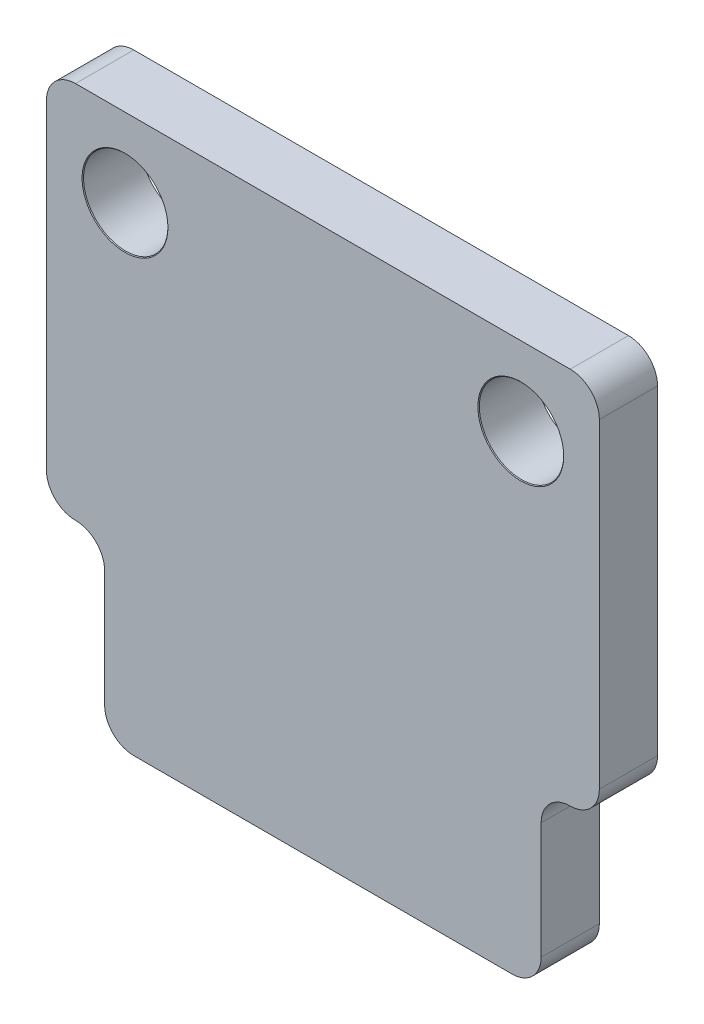
SolidWorks part; units mm, degrees
ref_plane "Plan de face" through (0, 0, 0) normal (0, 0, 1) x (1, 0, 0)
ref_plane "Plan de dessus" through (0, 0, 0) normal (0, 1, 0) x (1, 0, 0)
ref_plane "Plan de droite" through (0, 0, 0) normal (1, 0, 0) x (0, 0, -1)
sketch "Esquisse1" plane through (0, 0, 0) normal (0, 0, 1) x (1, 0, 0)
  line L0 (0, 0) -> (0, 19) construction
  line L1 (-9.5, 19) -> (9.5, 19)
  line L2 (9.5, 19) -> (9.5, 6)
  line L3 (9.5, 6) -> (7.5, 6)
  line L4 (7.5, 6) -> (7.5, 0)
  line L5 (7.5, 0) -> (-7.5, 0)
  line L6 (-7.5, 6) -> (-7.5, 0)
  line L7 (-9.5, 6) -> (-7.5, 6)
  line L8 (-9.5, 19) -> (-9.5, 6)
  dimension "D2" = 19
  dimension "D4" = 6
  dimension "D1" = 19
  dimension "D3" = 15
extrude "Boss.-Extru.1" add sketch "Esquisse1" along normal blind 2
fillet "Congé3" radius 1 8 edges at (9.5, 19, 1) (9.5, 6, 1) (7.5, 6, 1) (7.5, 0, 1) (-7.5, 0, 1) (-7.5, 6, 1) (-9.5, 6, 1) (-9.5, 19, 1)
hole_wizard "Dégagement M2.51" positions "Esquisse3D1" profile "Esquisse2" hole size "M2.5" standard "Ansi Metric" end condition through all
sketch3d "Esquisse3D1"
  line L0 (-9.5, 18, 2) -> (-9.5, 7, 2) construction
  line L1 (8.5, 19, 2) -> (-8.5, 19, 2) construction
  line L2 (9.5, 7, 2) -> (9.5, 18, 2) construction
  point P0 (-6.8, 16.3, 2)
  point P2 (6.8, 16.3, 2)
  dimension "D1" = 2.7
  dimension "D2" = 2.7
  dimension "D3" = 2.7
  dimension "D4" = 2.7
sketch "Esquisse2" plane through (-6.8, 16.3, 2) normal (1, 0, 0) x (0, -1, 0)
  line L0 (0, 0) -> (0, 2)
  line L1 (0, 2) -> (1.45, 2)
  line L2 (1.45, 2) -> (1.45, 0.025)
  line L3 (1.45, 0.025) -> (1.475, 0)
  line L5 (1.475, 0) -> (0, 0)
  line L6 (-1.45, 0.025) -> (-1.475, 0) construction
  line L11 (0, -6.35) -> (0, 107.95) construction
  dimension "Diamètre du perçage jusqu'au prochain" = 2.9
  dimension "Profondeur du perçage jusqu'au prochain" = 2
  dimension "Diamètre du fraisage entrant" = 2.95
  dimension "Angle du fraisage entrant" = 90
